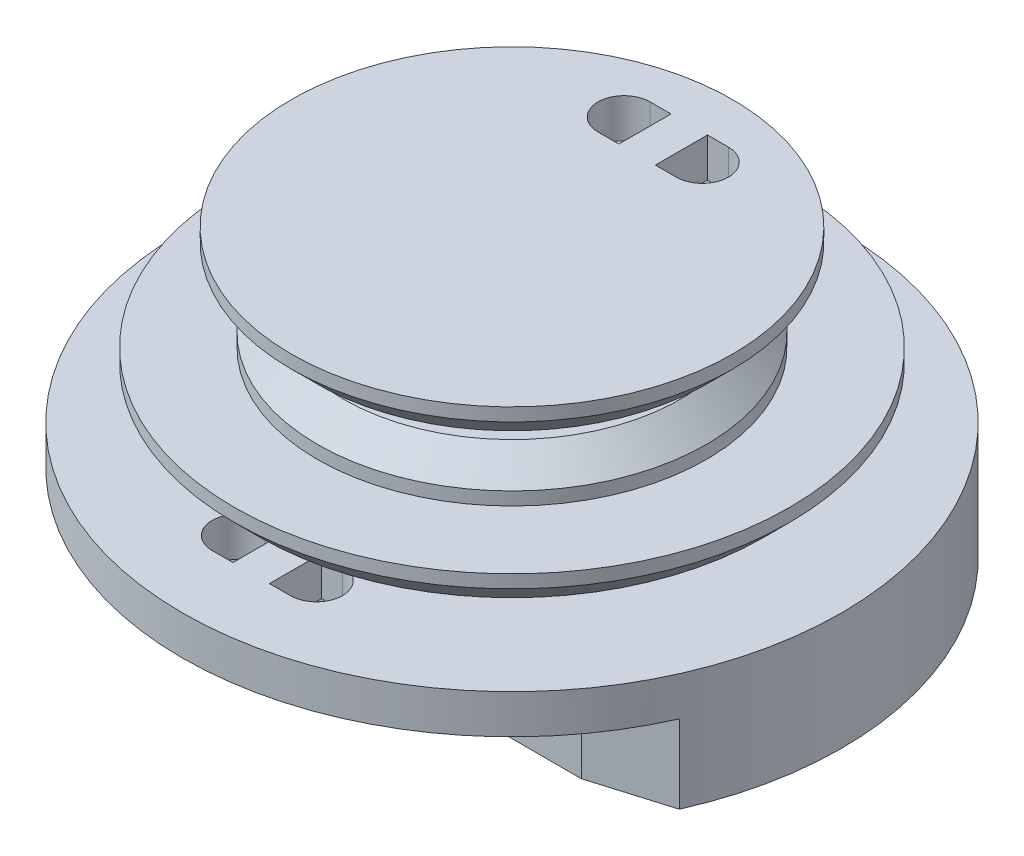
SolidWorks part; units mm, degrees
ref_plane "Front Plane" through (0, 0, 0) normal (0, 0, 1) x (1, 0, 0)
ref_plane "Top Plane" through (0, 0, 0) normal (0, 1, 0) x (1, 0, 0)
ref_plane "Right Plane" through (0, 0, 0) normal (1, 0, 0) x (0, 0, -1)
sketch "24" plane through (0, 0, 0) normal (0, 1, 0) x (1, 0, 0)
  circle A0 centre (0, 0) radius 7.6433
  dimension "D1" = 15.2866
extrude "Boss-Extrude1" add sketch "24" along normal blind 4
sketch "Sketch3" plane through (0, 0, 0) normal (0, 0, 1) x (1, 0, 0)
  line L0 (-7.6433, 4) -> (-10.6433, 4)
  line L1 (-10.6433, 4) -> (-10.6433, 2.5)
  line L5 (-12.6433, 1.5) -> (-12.6433, 0)
  line L6 (-7.6433, 4) -> (-7.6433, 0)
  line L7 (-12.6433, 0) -> (-7.6433, 0)
  line L8 (-10.6433, 2.5) -> (-7.6433, 2.5)
  line L9 (-7.6433, 2.5) -> (-7.6433, 1.5)
  line L10 (-7.6433, 1.5) -> (-12.6433, 1.5)
  dimension "D1" = 3
  dimension "D2" = 1.5
  dimension "D4" = 5
sketch "Sketch4" plane through (0, 0, 0) normal (1, 0, 0) x (0, 0, -1)
  line L0 (0, 4) -> (0, 0) construction
  line L1 (7.6433, 4) -> (-7.6433, 4) construction
revolve "Revolve1" add sketch "Sketch3" angle 360 about L0 region at (-9.1433, 3.25, 0) region at (-10.1433, 0.75, 0)
sketch "Sketch5" plane through (0, 4, 0) normal (0, 1, 0) x (1, 0, 0)
  circle A0 centre (0, 0) radius 4.4586
  dimension "D1" = 8.9172
extrude "Boss-Extrude2" add sketch "Sketch5" along normal blind 4
sketch "Sketch6" plane through (0, 0, 0) normal (0, 0, 1) x (1, 0, 0)
  line L0 (-4.4586, 8) -> (-8.4586, 8)
  line L1 (-8.4586, 8) -> (-8.4586, 6.5)
  line L3 (-8.4586, 6.5) -> (-4.4586, 6.5)
  line L6 (10.6433, 4) -> (-10.6433, 4) construction
  line L7 (-7.4586, 4) -> (-4.4586, 4)
  line L9 (-4.4586, 8) -> (-4.4586, 4)
  line L12 (-7.4586, 5.5) -> (-7.4586, 4)
  line L13 (-4.4586, 6.5) -> (-4.4586, 5.5)
  line L14 (-4.4586, 5.5) -> (-7.4586, 5.5)
  dimension "D1" = 4
  dimension "D2" = 1.5
  dimension "D3" = 3
revolve "Revolve2" add sketch "Sketch6" angle 360 about L0 region at (-6.4586, 7.25, 0) region at (-5.9586, 4.75, 0)
sketch "Sketch8" plane through (0, 0, 0) normal (0, -1, 0) x (1, 0, 0)
  line L0 (-1.5, 9) -> (1.5, 9) construction
  line L1 (-1.5, 10) -> (1.5, 10)
  line L2 (-1.5, 8) -> (1.5, 8)
  line L3 (0, 9) -> (0, 0) construction
  line L4 (0, 10) -> (0, 8) construction
  line L5 (-0.7, 10) -> (-0.7, 8)
  line L6 (0.7, 10) -> (0.7, 8)
  arc A0 (-1.5, 10) -> (-1.5, 8) centre (-1.5, 9) ccw
  arc A1 (1.5, 8) -> (1.5, 10) centre (1.5, 9) ccw
  circle A2 centre (0, 0) radius 12.6433 construction
  point P2 (0, 9)
  point P7 (2.5, 9)
  point P8 (-2.5, 9)
  dimension "D1" = 2
  dimension "D2" = 5
  dimension "D3" = 9
  dimension "D4" = 0.7
  dimension "D5" = 0.7
extrude "Cut-Extrude2" cut sketch "Sketch8" against normal blind 2 contours L1 A0 L2 L5 | L2 A1 L1 L6 region at (-1.5084, 0, 9) region at (1.5084, 0, 9)
sketch "Sketch9" plane through (0, 8, -8) normal (0, -1, 0) x (-1, 0, 0)
  line L0 (-1.5, -2.2) -> (1.5, -2.2) construction
  line L1 (-1.5, -1.2) -> (1.5, -1.2)
  line L2 (-1.5, -3.2) -> (1.5, -3.2)
  line L3 (0, -2.2) -> (0, -8) construction
  line L4 (0, -1.2) -> (0, -3.2) construction
  line L5 (-0.7, -1.2) -> (-0.7, -3.2)
  line L6 (0.7, -1.2) -> (0.7, -3.2)
  arc A0 (-1.5, -1.2) -> (-1.5, -3.2) centre (-1.5, -2.2) ccw
  arc A1 (1.5, -3.2) -> (1.5, -1.2) centre (1.5, -2.2) ccw
  point P2 (0, -2.2)
  point P7 (2.5, -2.2)
  point P8 (-2.5, -2.2)
  dimension "D1" = 2
  dimension "D2" = 5
  dimension "D3" = 5.8
  dimension "D4" = 0.7
  dimension "D5" = 0.7
extrude "Cut-Extrude3" cut sketch "Sketch9" along normal blind 2 contours A0 L1 L5 L2 | A1 L2 L6 L1 region at (1.5084, 8, -5.8) region at (-1.5084, 8, -5.8)
sketch "Sketch10" plane through (0, 0, 0) normal (0, -1, 0) x (1, 0, 0)
  line L0 (-11.1289, 6) -> (11.1289, 6)
  line L2 (-12.6433, 0) -> (12.6433, 0) construction
  line L3 (-7.25, 0) -> (0, 0) construction
  arc A1 (10.4428, -7.1275) -> (11.1289, 6) centre (0, 0) ccw
  circle A2 centre (-7.25, 0) radius 0.5
  circle A3 centre (7.25, 0) radius 0.5
  circle A4 centre (0, 0) radius 12.6433 construction
  arc A5 (-11.1289, 6) -> (11.1289, 6) centre (0, 0) ccw
  point P5 (0, 0)
  point P14 (0, 0)
  circle M5 centre (0, 0) radius 12.6433
  dimension "D4" = 1
  dimension "D2" = 6
  dimension "D5" = 7.25
  dimension "D6" = 7.25
extrude "Boss-Extrude4" add sketch "Sketch10" along normal blind 3 contours L0 A3 A2 M5 region at (0, 0, -2.3243)
chamfer "Chamfer1" distance 1 angle 45 5 edges at (0, 2.5, 10.6433) (0, 5.5, 7.4586) (0, 6.5, 8.4586) (11.1289, -1.5, 6) (-11.1289, -1.5, 6) first distance on face at (0, 2.5, 7.6433) first distance on face at (0, 4, 7.4586) first distance on face at (0, 6.5, 4.4586) first distance on face at (0, -1.5, 3) first distance on face at (0, -1.5, 6)
